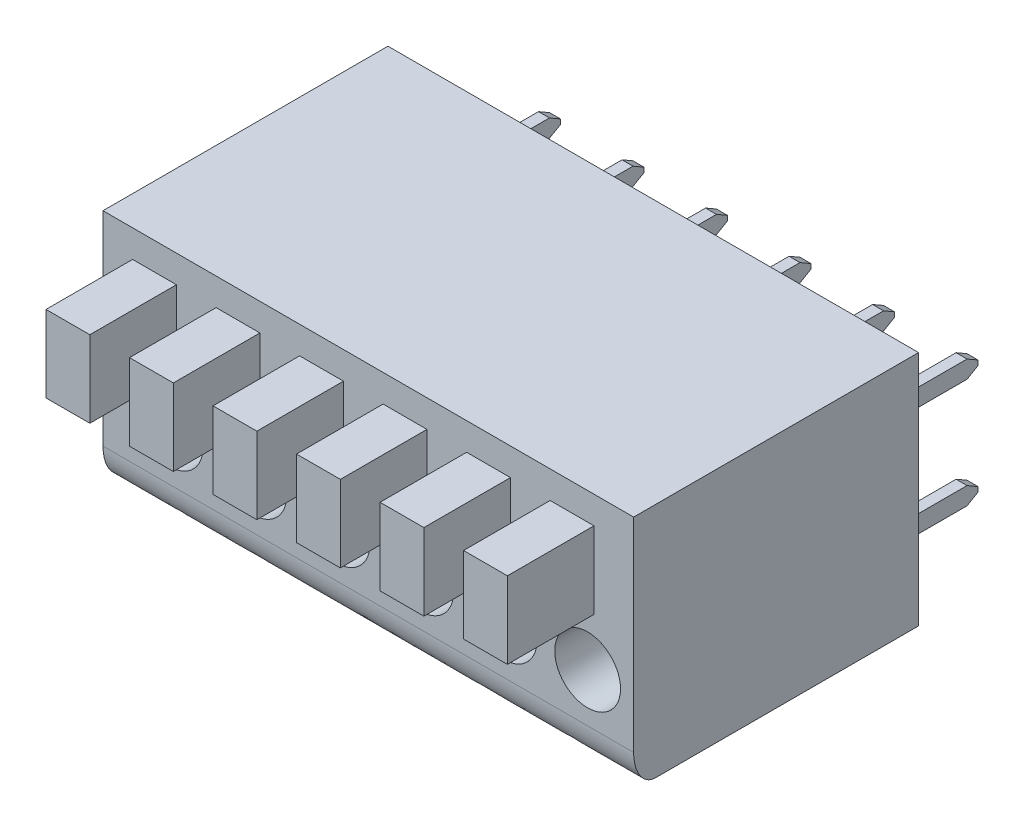
SolidWorks part; units mm, degrees
ref_plane "Спереди" through (0, 0, 0) normal (0, 0, 1) x (1, 0, 0)
ref_plane "Сверху" through (0, 0, 0) normal (0, 1, 0) x (1, 0, 0)
ref_plane "Справа" through (0, 0, 0) normal (1, 0, 0) x (0, 0, -1)
sketch "Эскиз1" plane through (0, 0, 0) normal (0, 0, 1) x (1, 0, 0)
  line L1 (-12.105, -5.4) -> (12.105, -5.4)
  line L2 (-12.105, -5.4) -> (-12.105, 5.4)
  line L3 (-12.105, 5.4) -> (12.105, 5.4)
  line L4 (12.105, -5.4) -> (12.105, 5.4)
  line L5 (-12.105, -5.4) -> (12.105, 5.4) construction
  line L6 (-12.105, 5.4) -> (12.105, -5.4) construction
  point P0 (0, 0)
  dimension "D1" = 24.21
  dimension "D2" = 10.8
extrude "Бобышка-Вытянуть1" add sketch "Эскиз1" along normal blind 13
fillet "Скругление1" radius 1 1 edges at (0, -5.4, 13) second distance 1.5 first distance on face at (0, -5.4, 6.5)
sketch "Эскиз2" plane through (0, 0, 13) normal (0, 0, 1) x (1, 0, 0)
  line L0 (12.105, -3.9) -> (12.105, 5.4) construction
  line L1 (8.295, 0.65) -> (10.295, 0.65)
  line L2 (8.295, 0.65) -> (8.295, 4.15)
  line L3 (8.295, 4.15) -> (10.295, 4.15)
  line L4 (10.295, 0.65) -> (10.295, 4.15)
  line L5 (8.295, 0.65) -> (10.295, 4.15) construction
  line L6 (8.295, 4.15) -> (10.295, 0.65) construction
  line L7 (12.105, 5.4) -> (-12.105, 5.4) construction
  point P0 (9.295, 2.4)
  dimension "D1" = 3.5
  dimension "D2" = 2
  dimension "D3" = 3.81
  dimension "D4" = 4.75
extrude "Бобышка-Вытянуть2" add sketch "Эскиз2" along normal blind 3.95
sketch "Эскиз3" plane through (0, 0, 13) normal (0, 0, 1) x (1, 0, 0)
  line L0 (12.105, -3.9) -> (12.105, 5.4) construction
  circle A0 centre (10.005, -1.686) radius 1.5
  dimension "D1" = 3
  dimension "D2" = 2.1
extrude "Вырез-Вытянуть1" cut sketch "Эскиз3" against normal blind 3.95
sketch "Эскиз4" plane through (0, 0, 0) normal (0, 0, -1) x (-1, 0, 0)
  line L0 (-12.105, 5.4) -> (12.105, 5.4) construction
  line L1 (-11.315, 2.45) -> (-10.815, 2.45)
  line L2 (-11.315, 2.45) -> (-11.315, 3.25)
  line L3 (-11.315, 3.25) -> (-10.815, 3.25)
  line L4 (-10.815, 2.45) -> (-10.815, 3.25)
  line L5 (-11.315, 2.45) -> (-10.815, 3.25) construction
  line L6 (-11.315, 3.25) -> (-10.815, 2.45) construction
  line L7 (-10.815, -1.75) -> (-11.315, -1.75)
  line L8 (-10.815, -1.75) -> (-10.815, -2.55)
  line L9 (-10.815, -2.55) -> (-11.315, -2.55)
  line L10 (-11.315, -1.75) -> (-11.315, -2.55)
  line L11 (-10.815, -1.75) -> (-11.315, -2.55) construction
  line L12 (-10.815, -2.55) -> (-11.315, -1.75) construction
  line L14 (-12.105, -5.4) -> (-12.105, 5.4) construction
  point P0 (-11.065, 2.85)
  point P5 (-11.065, -2.15)
  dimension "D1" = 0.5
  dimension "D2" = 0.8
  dimension "D3" = 5
  dimension "D4" = 2.55
  dimension "D5" = 1.04
extrude "Бобышка-Вытянуть3" add sketch "Эскиз4" along normal blind 3.5
chamfer "Фаска1" distance 0.5 angle 30 4 edges at (11.065, -2.55, -3.5) (11.065, -1.75, -3.5) (11.065, 2.45, -3.5) (11.065, 3.25, -3.5) first distance on face at (11.065, -2.55, -1.75) first distance on face at (11.065, -1.75, -1.75) first distance on face at (11.065, 2.45, -1.75) first distance on face at (11.065, 3.25, -1.75)
pattern_linear "Линейный массив2" count 6 spacing 3.81 along (-1, 0, 0) of "Бобышка-Вытянуть2", "Вырез-Вытянуть1", "Бобышка-Вытянуть3", "Фаска1"
